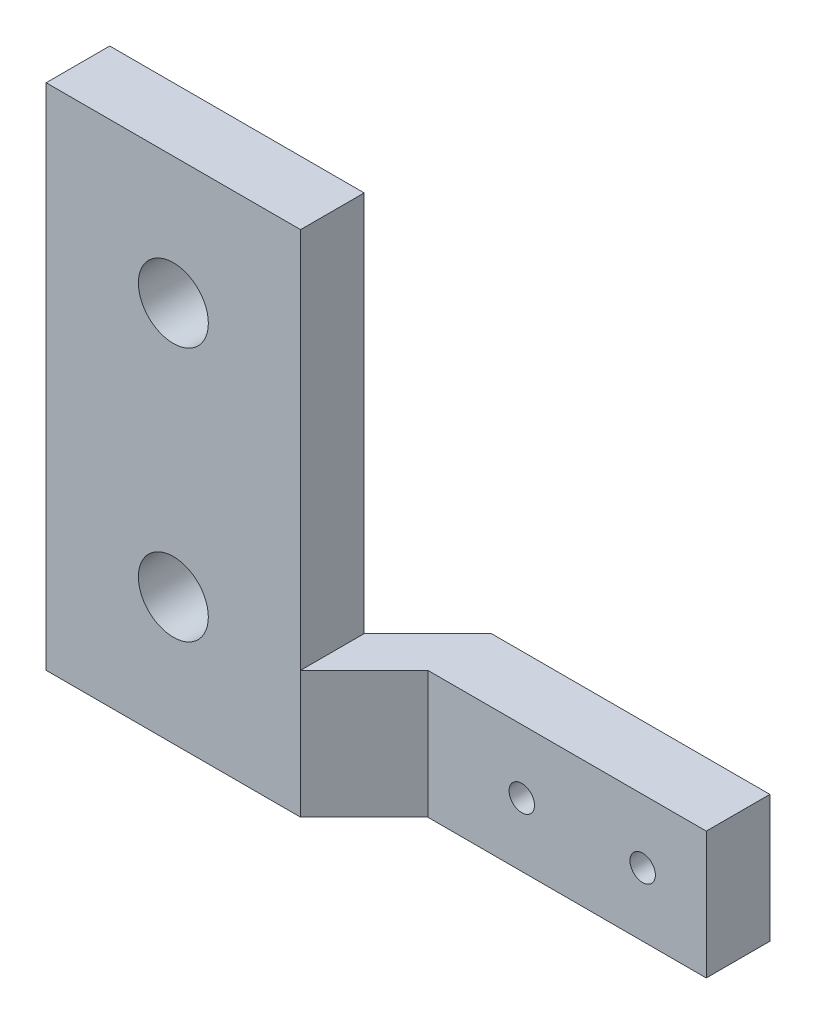
SolidWorks part; units mm, degrees
ref_plane "Plan de face" through (0, 0, 0) normal (0, 0, 1) x (1, 0, 0)
ref_plane "Plan de dessus" through (0, 0, 0) normal (0, 1, 0) x (1, 0, 0)
ref_plane "Plan de droite" through (0, 0, 0) normal (1, 0, 0) x (0, 0, -1)
sketch "Esquisse1" plane through (0, 0, 0) normal (0, 0, 1) x (1, 0, 0)
  line L0 (-27.8251, 6.7177) -> (-27.8251, -13.2823) construction
  line L2 (-37.8251, 16.7177) -> (-37.8251, -23.2823)
  line L8 (-37.8251, 16.7177) -> (-17.8251, 16.7177)
  line L9 (-17.8251, 16.7177) -> (-17.8251, -23.2823)
  line L12 (-37.8251, -23.2823) -> (-17.8251, -23.2823)
  circle A0 centre (-27.8251, 6.7177) radius 2.75
  circle A1 centre (-27.8251, -13.2823) radius 2.75
  point P8 (-27.8251, -3.2823)
  point P10 (-37.8251, -3.2823)
  point P17 (-27.8251, 16.7177)
  dimension "D3" = 5.5
  dimension "D1" = 20
  dimension "D2" = 40
  dimension "D5" = 20
extrude "Boss.-Extru.1" add sketch "Esquisse1" along normal blind 5
sketch "Esquisse2" plane through (0, -23.2823, 0) normal (0, -1, 0) x (1, 0, 0)
  line L0 (-17.8251, 0) -> (-17.8251, 5)
  line L1 (-17.8251, 5) -> (-12.8251, 0)
  line L2 (-12.8251, 0) -> (9.0631, 0)
  line L3 (9.0631, 0) -> (9.0631, -5)
  line L4 (9.0631, -5) -> (-12.8251, -5)
  line L5 (-12.8251, -5) -> (-17.8251, 0)
  dimension "D1" = 45
  dimension "D2" = 5
  dimension "D3" = 5
extrude "Boss.-Extru.2" add sketch "Esquisse2" against normal blind 10
sketch "Esquisse3" plane through (0, 0, 0) normal (0, 0, 1) x (1, 0, 0)
  line L0 (4.0631, -18.2823) -> (-5.4369, -18.2823) construction
  line L1 (9.0631, -13.2823) -> (9.0631, -23.2823) construction
  line L2 (9.0631, -13.2823) -> (-12.8251, -13.2823) construction
  circle A0 centre (4.0631, -18.2823) radius 1
  circle A1 centre (-5.4369, -18.2823) radius 1
  dimension "D4" = 2
  dimension "D1" = 9.5
  dimension "D2" = 5
  dimension "D3" = 5
extrude "Enlèv. mat.-Extru.1" cut sketch "Esquisse3" against normal up to next
